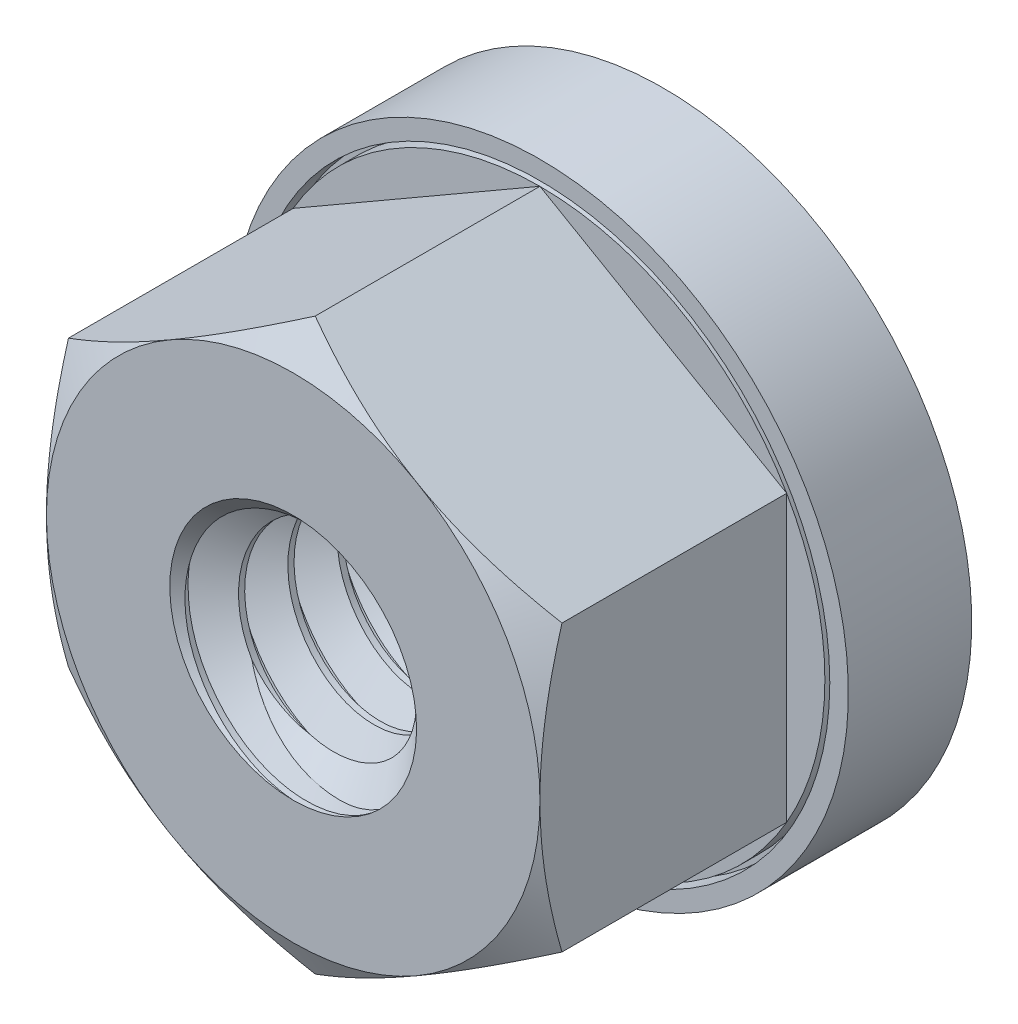
SolidWorks part; units mm, degrees
ref_plane "Front Plane" through (0, 0, 0) normal (0, 0, 1) x (1, 0, 0)
ref_plane "Top Plane" through (0, 0, 0) normal (0, 1, 0) x (1, 0, 0)
ref_plane "Right Plane" through (0, 0, 0) normal (1, 0, 0) x (0, 0, -1)
sketch "Sketch1" plane through (0, 0, 0) normal (0, 0, 1) x (1, 0, 0)
  line L1 (0, 7.3323) -> (-6.35, 3.6662)
  line L2 (-6.35, 3.6662) -> (-6.35, -3.6662)
  line L3 (-6.35, -3.6662) -> (0, -7.3323)
  line L4 (0, -7.3323) -> (6.35, -3.6662)
  line L5 (6.35, -3.6662) -> (6.35, 3.6662)
  line L6 (6.35, 3.6662) -> (0, 7.3323)
  circle A0 centre (0, 0) radius 6.35 construction
  dimension "Hex" = 12.7
extrude "Extrude1" add sketch "Sketch1" against normal blind 9.525
sketch "Sketch2" plane through (0, 0, 0) normal (0, 0, 1) x (1, 0, 0)
  circle A0 centre (0, 0) radius 6.35 construction
  circle A1 centre (0, 0) radius 6.35
extrude "Cut-Extrude1" cut sketch "Sketch2" against normal through all draft 60 flip side to cut
sketch "Sketch13" plane through (0, 0, -9.525) normal (0, 0, -1) x (-1, 0, 0)
  circle A0 centre (0, 0) radius 7.9375
  dimension "D1" = 15.875
extrude "Extrude3" add sketch "Sketch13" against normal blind 3.175
sketch "Sketch4" plane through (0, 0, 0) normal (0, 0, 1) x (1, 0, 0)
  circle A0 centre (0, 0) radius 3.175
  dimension "Thread Dia" = 6.35
extrude "Cut-Extrude3" cut sketch "Sketch4" against normal through all
sketch "Sketch3" plane through (0, 0, -9.525) normal (0, 0, -1) x (-1, 0, 0)
  circle A1 centre (0, 0) radius 6.35
  circle A2 centre (0, 0) radius 6.35
  dimension "D1" = 0
sketch "Sketch7" plane through (0, 0, 0) normal (0, 0, 1) x (1, 0, 0)
  circle A0 centre (0, 0) radius 3.175 construction
  circle A5 centre (0, 0) radius 3.175
sketch "Sketch8" plane through (0, 0, -9.525) normal (0, 0, -1) x (-1, 0, 0)
  circle A1 centre (0, 0) radius 3.175
  circle A2 centre (0, 0) radius 3.175 construction
sketch "Sketch5" plane through (0, 0, 0) normal (0, 0, 1) x (1, 0, 0)
  circle A0 centre (0, 0) radius 3.175 construction
  circle A1 centre (0, 0) radius 3.175
curve "Helix/Spiral1" pitch 1.27 height 10.795 turns 8.5 parameters "pitch"=1.27
sketch "Sketch9" plane through (0, 0, 0) normal (1, 0, 0) x (0, 0, -1)
  line L0 (-0.635, 3.175) -> (-0.4762, 3.175)
  line L1 (-0.4762, 3.175) -> (0, 2.3501)
  line L2 (-0.635, 3.175) -> (-1.1112, 2.3501)
  line L3 (-1.1112, 2.3501) -> (0, 2.3501)
  line L4 (-0.5556, 3.175) -> (-0.5556, 2.3501) construction
  line L5 (-0.8731, 2.7626) -> (-0.2381, 2.7626) construction
  line L7 (0, 2.3501) -> (0, 3.175) construction
  line L8 (0, 3.175) -> (0, -3.175) construction
  dimension "D1" = 0.1588
  dimension "D2" = 0.635
  dimension "D3" = 60
sketch "Sketch12" plane through (0, 0, 0) normal (0, 0, 1) x (1, 0, 0)
  circle A0 centre (0, 0) radius 2.3501
  circle A1 centre (0, 0) radius 3.175 construction
  circle A2 centre (0, 0) radius 3.175
extrude "Extrude2" add sketch "Sketch12" against normal up to surface (9.525 mm away)
sweep "Cut-Sweep1" cut profiles "Sketch9" path "Helix/Spiral1"
extrude "Cut-Extrude6" cut sketch "Sketch7" against normal through all draft 45
extrude "Cut-Extrude7" cut sketch "Sketch8" against normal through all draft 45
sketch "Sketch14" plane through (0, 0, -6.35) normal (0, 0, 1) x (1, 0, 0)
  circle A0 centre (0, 0) radius 7.3323
extrude "Cut-Extrude-Thin1" cut sketch "Sketch14" against normal blind 0.508 thin
equation "\"D2@Sketch9\" = \"pitch@Helix/Spiral1\"*.5"
equation "\"D3@Helix/Spiral1\" = \"pitch@Helix/Spiral1\"+\"Height@Extrude1\""
equation "\"D1@Sketch9\" = \"pitch@Helix/Spiral1\"*.125"
